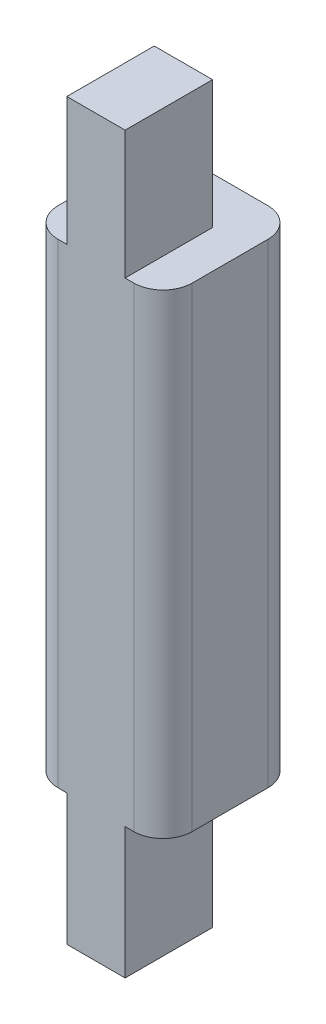
SolidWorks part; units mm, degrees
ref_plane "Front Plane" through (0, 0, 0) normal (0, 0, 1) x (1, 0, 0)
ref_plane "Top Plane" through (0, 0, 0) normal (0, 1, 0) x (1, 0, 0)
ref_plane "Right Plane" through (0, 0, 0) normal (1, 0, 0) x (0, 0, -1)
sketch "Sketch2" plane through (0, 0, 0) normal (0, 1, 0) x (1, 0, 0)
  line L0 (0, -11.5) -> (0, 11.5) construction
  line L1 (-11.5, -11.5) -> (11.5, -11.5)
  line L2 (-11.5, -11.5) -> (-11.5, 11.5)
  line L3 (-11.5, 11.5) -> (11.5, 11.5)
  line L4 (11.5, -11.5) -> (11.5, 11.5)
  line L5 (-11.5, -11.5) -> (11.5, 11.5) construction
  line L6 (-11.5, 11.5) -> (11.5, -11.5) construction
  line L7 (-5, -11.5) -> (5, -11.5)
  line L8 (-5, -11.5) -> (-5, 3.5)
  line L9 (-5, 3.5) -> (5, 3.5)
  line L10 (5, -11.5) -> (5, 3.5)
  point P0 (0, 0)
  point P10 (0, 3.5)
  point P13 (0, 0)
  dimension "D1" = 23
  dimension "D2" = 10
  dimension "D3" = 15
extrude "Boss-Extrude1" add sketch "Sketch2" along normal blind 81.5 contours L10 L1 L4 L3 L2 L8 L9 | L1 L10 L9 L8 region at (-11.1747, 0, 0) region at (0, 0, 4)
extrude "Boss-Extrude2" add sketch "Sketch2<3>" against normal blind 22.5 contours L1 L10 L9 L8 region at (0, 0, 4)
sketch "Sketch2<3>" plane through (0, 0, 0) normal (0, 1, 0) x (1, 0, 0) same geometry as "Sketch2"
sketch "Sketch3" plane through (11.5, 0, 0) normal (1, 0, 0) x (0, 0, -1)
  line L0 (-11.5, 81.5) -> (11.547, -0.5278) construction
  line L1 (-30.2664, 40.4861) -> (30.3134, 40.4861) construction
  point P6 (0.0235, 40.4861)
ref_plane "Plane1" through (0, 40.4861, 0) normal (0, 1, 0) x (1, 0, 0)
fillet "Fillet1" radius 5 4 edges at (-11.5, 40.75, 11.5) (11.5, 40.75, 11.5) (-11.5, 40.75, -11.5) (11.5, 40.75, -11.5)
mirror "Mirror1" about plane through (0, 40.4861, 0) normal (0, 1, 0) of "Boss-Extrude2"
